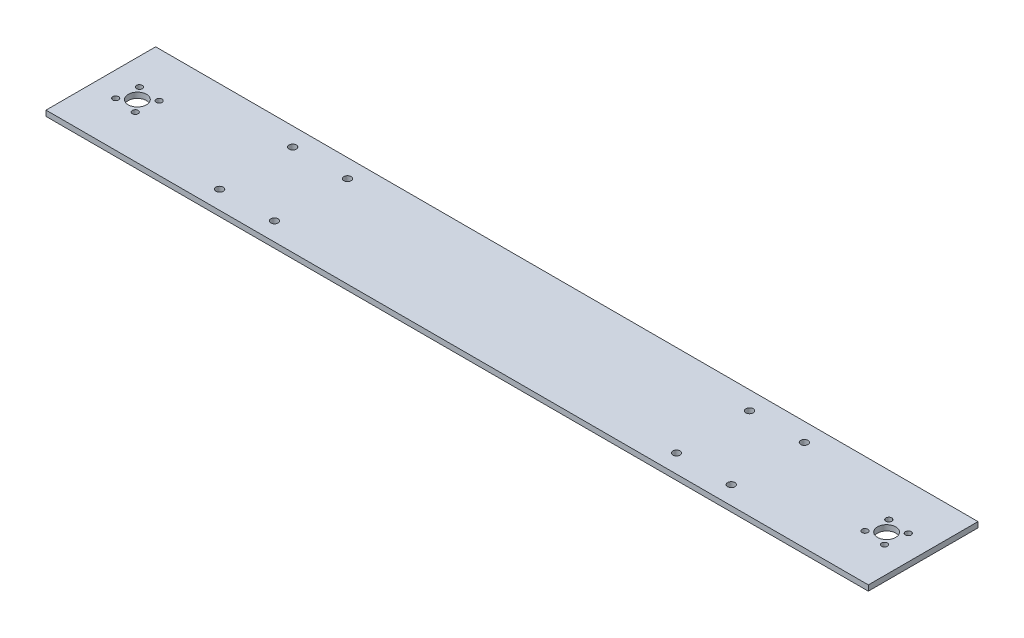
SolidWorks part; units mm, degrees
material "3.0515 (EN-AW 3103)"
ref_plane "Płaszczyzna przednia" through (0, 0, 0) normal (0, 0, 1) x (1, 0, 0)
ref_plane "Płaszczyzna górna" through (0, 0, 0) normal (0, 1, 0) x (1, 0, 0)
ref_plane "Płaszczyzna prawa" through (0, 0, 0) normal (1, 0, 0) x (0, 0, -1)
sketch "Szkic1" plane through (0, 0, 0) normal (0, 1, 0) x (1, 0, 0)
  line L1 (0, 0) -> (-450, 0)
  line L2 (0, 0) -> (0, 60)
  line L3 (0, 60) -> (-450, 60)
  line L4 (-450, 0) -> (-450, 60)
  dimension "D1" = 60
  dimension "D2" = 450
extrude "Dodanie-wyciągnięcie1" add sketch "Szkic1" along normal blind 3
hole_wizard "Otwór pod śrubę M41" positions "Szkic6" profile "Szkic7" hole size "M4" standard "Ansi Metric" end condition through all
sketch "Szkic6" plane through (0, 3, 0) normal (0, 1, 0) x (1, 0, 0)
  line L0 (0, 60) -> (-450, 60) construction
  line L1 (-450, 0) -> (0, 0) construction
  line L2 (-450, 60) -> (-450, 0) construction
  line L3 (0, 0) -> (0, 60) construction
  point P0 (-365, 50)
  point P2 (-335, 50)
  point P4 (-365, 10)
  point P6 (-335, 10)
  point P8 (-115, 50)
  point P10 (-85, 50)
  point P12 (-115, 10)
  point P14 (-85, 10)
  dimension "D1" = 10
  dimension "D2" = 10
  dimension "D3" = 30
  dimension "D4" = 30
  dimension "D5" = 30
  dimension "D6" = 30
  dimension "D7" = 85
  dimension "D8" = 85
  dimension "D9" = 85
  dimension "D10" = 85
sketch "Szkic7" plane through (-365, 3, -50) normal (1, 0, 0) x (0, 0, 1)
  line L0 (0, 0) -> (0, 3)
  line L1 (0, 3) -> (2, 3)
  line L2 (2, 3) -> (2, 0)
  line L5 (2, 0) -> (0, 0)
  line L11 (0, -6.35) -> (0, 107.95) construction
  dimension "Œrednica otworu na wylot" = 4
  dimension "G³êbokoœæ otworu na wylot" = 3
sketch "Szkic8" plane through (0, 3, 0) normal (0, 1, 0) x (1, 0, 0)
  line L0 (0, 60) -> (-450, 60) construction
  line L2 (0, 0) -> (0, 60) construction
  line L3 (-450, 60) -> (-450, 0) construction
  circle A0 centre (-20, 30) radius 5
  circle A1 centre (-430, 30) radius 5
  dimension "D1" = 10
  dimension "D2" = 30
  dimension "D3" = 20
  dimension "D4" = 10
  dimension "D5" = 30
  dimension "D6" = 20
extrude "Wytnij-wyciągnięcie1" cut sketch "Szkic8" against normal blind 10
sketch "Szkic9" plane through (0, 3, 0) normal (0, 1, 0) x (1, 0, 0)
  circle A0 centre (-435.3563, 36.5109) radius 1.6
  circle A1 centre (-436.5109, 24.6437) radius 1.6
  circle A2 centre (-424.6437, 23.4891) radius 1.6
  circle A3 centre (-423.4891, 35.3563) radius 1.6
extrude "Wytnij-wyciągnięcie2" cut sketch "Szkic9" against normal through all
sketch "Szkic10" plane through (0, 3, 0) normal (0, 1, 0) x (1, 0, 0)
  circle A0 centre (-13.4891, 35.3563) radius 1.6
  circle A1 centre (-14.6437, 23.4891) radius 1.6
  circle A2 centre (-26.5109, 24.6437) radius 1.6
  circle A4 centre (-25.3457, 36.555) radius 1.6
  dimension "D1" = 3.2
extrude "Wytnij-wyciągnięcie3" cut sketch "Szkic10" against normal blind 10
